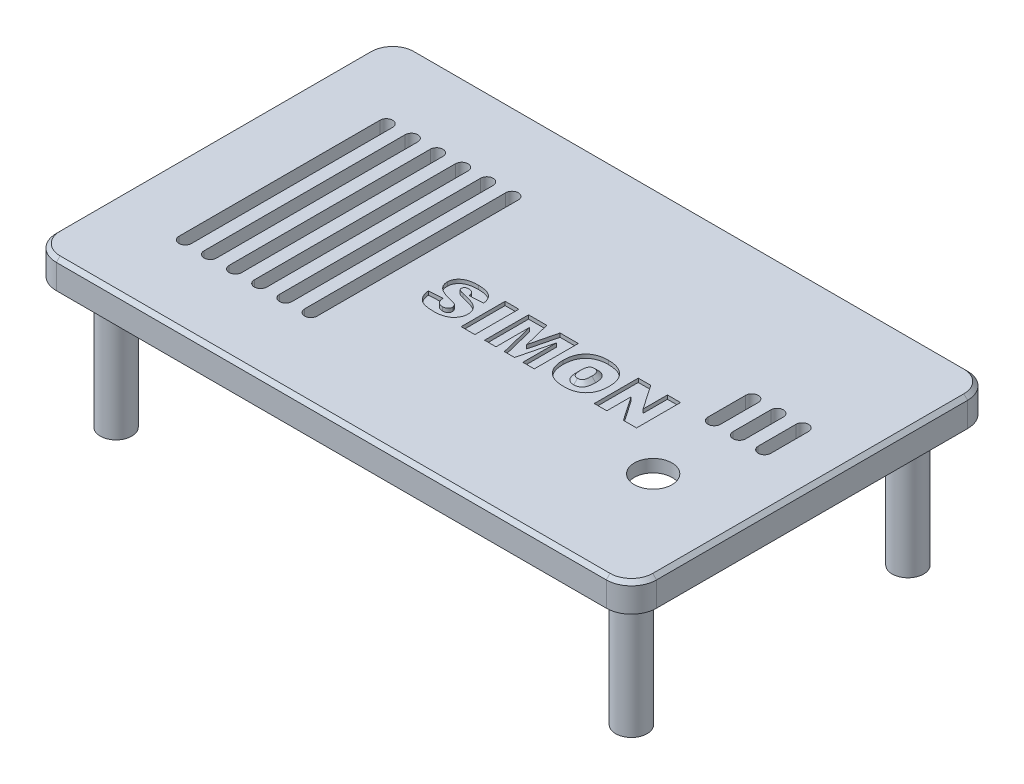
SolidWorks part; units mm, degrees
ref_plane "Front Plane" through (0, 0, 0) normal (0, 0, 1) x (1, 0, 0)
ref_plane "Top Plane" through (0, 0, 0) normal (0, 1, 0) x (1, 0, 0)
ref_plane "Right Plane" through (0, 0, 0) normal (1, 0, 0) x (0, 0, -1)
sketch "Croquis_tapa" plane through (0, 0, 0) normal (0, 1, 0) x (1, 0, 0)
  line L0 (-43.75, -28.75) -> (43.75, -28.75)
  line L1 (47.75, -24.75) -> (47.75, 24.75)
  line L2 (43.75, 28.75) -> (-43.75, 28.75)
  line L3 (-47.75, 24.75) -> (-47.75, -24.75)
  arc A0 (43.75, -28.75) -> (47.75, -24.75) centre (43.75, -24.75) ccw
  arc A1 (47.75, 24.75) -> (43.75, 28.75) centre (43.75, 24.75) ccw
  arc A2 (-43.75, 28.75) -> (-47.75, 24.75) centre (-43.75, 24.75) ccw
  arc A3 (-47.75, -24.75) -> (-43.75, -28.75) centre (-43.75, -24.75) ccw
  dimension "D3" = 4
  dimension "D1" = 95.5
  dimension "D2" = 57.5
extrude "Tapa" add sketch "Croquis_tapa" along normal blind 2
sketch "Croquis_falda" plane through (0, 0, 0) normal (0, 1, 0) x (1, 0, 0)
  line L0 (-43.75, -28.75) -> (43.75, -28.75)
  line L1 (47.75, -24.75) -> (47.75, 24.75)
  line L2 (43.75, 28.75) -> (-43.75, 28.75)
  line L3 (-47.75, 24.75) -> (-47.75, -24.75)
  line L4 (-43.75, -27.7) -> (43.75, -27.7)
  line L5 (46.7, -24.75) -> (46.7, 24.75)
  line L6 (43.75, 27.7) -> (-43.75, 27.7)
  line L7 (-46.7, 24.75) -> (-46.7, -24.75)
  arc A0 (43.75, -28.75) -> (47.75, -24.75) centre (43.75, -24.75) ccw
  arc A1 (47.75, 24.75) -> (43.75, 28.75) centre (43.75, 24.75) ccw
  arc A2 (-43.75, 28.75) -> (-47.75, 24.75) centre (-43.75, 24.75) ccw
  arc A3 (-47.75, -24.75) -> (-43.75, -28.75) centre (-43.75, -24.75) ccw
  arc A4 (43.75, -27.7) -> (46.7, -24.75) centre (43.75, -24.75) ccw
  arc A5 (46.7, 24.75) -> (43.75, 27.7) centre (43.75, 24.75) ccw
  arc A6 (-43.75, 27.7) -> (-46.7, 24.75) centre (-43.75, 24.75) ccw
  arc A7 (-46.7, -24.75) -> (-43.75, -27.7) centre (-43.75, -24.75) ccw
  dimension "D3" = 2.95
  dimension "D1" = 93.4
  dimension "D2" = 55.4
extrude "Escalon_groove" add sketch "Croquis_falda" against normal blind 2.5
sketch "Croquis_postes" plane through (0, 0, 0) normal (0, 1, 0) x (1, 0, 0)
  circle A0 centre (41, 22) radius 2.5
  circle A1 centre (41, -22) radius 2.5
  circle A2 centre (-41, 22) radius 2.5
  circle A3 centre (-41, -22) radius 2.5
  dimension "D1" = 5
extrude "Postes_PCB" add sketch "Croquis_postes" against normal blind 23.3
sketch "Croquis_ventana_y_ventilas" plane through (0, 0, 0) normal (0, 1, 0) x (1, 0, 0)
  line L0 (-16, -16) -> (-16, 16) construction
  line L1 (-17, -16) -> (-17, 16)
  line L2 (-15, -16) -> (-15, 16)
  line L3 (-20, -16) -> (-20, 16) construction
  line L4 (-21, -16) -> (-21, 16)
  line L5 (-19, -16) -> (-19, 16)
  line L6 (-24, -16) -> (-24, 16) construction
  line L7 (-25, -16) -> (-25, 16)
  line L8 (-23, -16) -> (-23, 16)
  line L9 (-28, -16) -> (-28, 16) construction
  line L10 (-29, -16) -> (-29, 16)
  line L11 (-27, -16) -> (-27, 16)
  line L12 (-32, -16) -> (-32, 16) construction
  line L13 (-33, -16) -> (-33, 16)
  line L14 (-31, -16) -> (-31, 16)
  line L15 (-36, -16) -> (-36, 16) construction
  line L16 (-37, -16) -> (-37, 16)
  line L17 (-35, -16) -> (-35, 16)
  line L18 (31, 1.18) -> (31, 7.18) construction
  line L19 (30, 1.18) -> (30, 7.18)
  line L20 (32, 1.18) -> (32, 7.18)
  line L21 (35, 1.18) -> (35, 7.18) construction
  line L22 (34, 1.18) -> (34, 7.18)
  line L23 (36, 1.18) -> (36, 7.18)
  line L24 (39, 1.18) -> (39, 7.18) construction
  line L25 (38, 1.18) -> (38, 7.18)
  line L26 (40, 1.18) -> (40, 7.18)
  circle A0 centre (33.46, -11) radius 3
  arc A1 (-17, -16) -> (-15, -16) centre (-16, -16) ccw
  arc A2 (-15, 16) -> (-17, 16) centre (-16, 16) ccw
  arc A3 (-21, -16) -> (-19, -16) centre (-20, -16) ccw
  arc A4 (-19, 16) -> (-21, 16) centre (-20, 16) ccw
  arc A5 (-25, -16) -> (-23, -16) centre (-24, -16) ccw
  arc A6 (-23, 16) -> (-25, 16) centre (-24, 16) ccw
  arc A7 (-29, -16) -> (-27, -16) centre (-28, -16) ccw
  arc A8 (-27, 16) -> (-29, 16) centre (-28, 16) ccw
  arc A9 (-33, -16) -> (-31, -16) centre (-32, -16) ccw
  arc A10 (-31, 16) -> (-33, 16) centre (-32, 16) ccw
  arc A11 (-37, -16) -> (-35, -16) centre (-36, -16) ccw
  arc A12 (-35, 16) -> (-37, 16) centre (-36, 16) ccw
  arc A13 (30, 1.18) -> (32, 1.18) centre (31, 1.18) ccw
  arc A14 (32, 7.18) -> (30, 7.18) centre (31, 7.18) ccw
  arc A15 (34, 1.18) -> (36, 1.18) centre (35, 1.18) ccw
  arc A16 (36, 7.18) -> (34, 7.18) centre (35, 7.18) ccw
  arc A17 (38, 1.18) -> (40, 1.18) centre (39, 1.18) ccw
  arc A18 (40, 7.18) -> (38, 7.18) centre (39, 7.18) ccw
  point P4 (-16, 0)
  point P9 (-20, 0)
  point P16 (-24, 0)
  point P23 (-28, 0)
  point P30 (-32, 0)
  point P37 (-36, 0)
  point P44 (31, 4.18)
  point P51 (35, 4.18)
  point P58 (39, 4.18)
  point P65 (0, 0)
  dimension "D1" = 6
extrude "Ventana_LDR_y_ventilas" cut sketch "Croquis_ventana_y_ventilas" along normal through all and the other way through all
ref_plane "Plano_Top Plane_+2" through (0, 2, 0) normal (0, 1, 0) x (1, 0, 0)
sketch "Croquis_texto" plane through (0, 2, 0) normal (0, 1, 0) x (1, 0, 0)
  text T0 "SIMON" font "Arial Black" height 7
extrude "Texto_SIMON" cut sketch "Croquis_texto" against normal blind 0.6
chamfer "Chaflan_cara_superior" distance 0.6 angle 45 12 edges at (-47.75, 2, 0) (-46.5784, 2, -27.5784) (0, 2, -28.75) (46.5784, 2, -27.5784) (47.75, 2, 0) (46.5784, 2, 27.5784) (0, 2, 28.75) (-46.5784, 2, 27.5784) tangent propagation no
